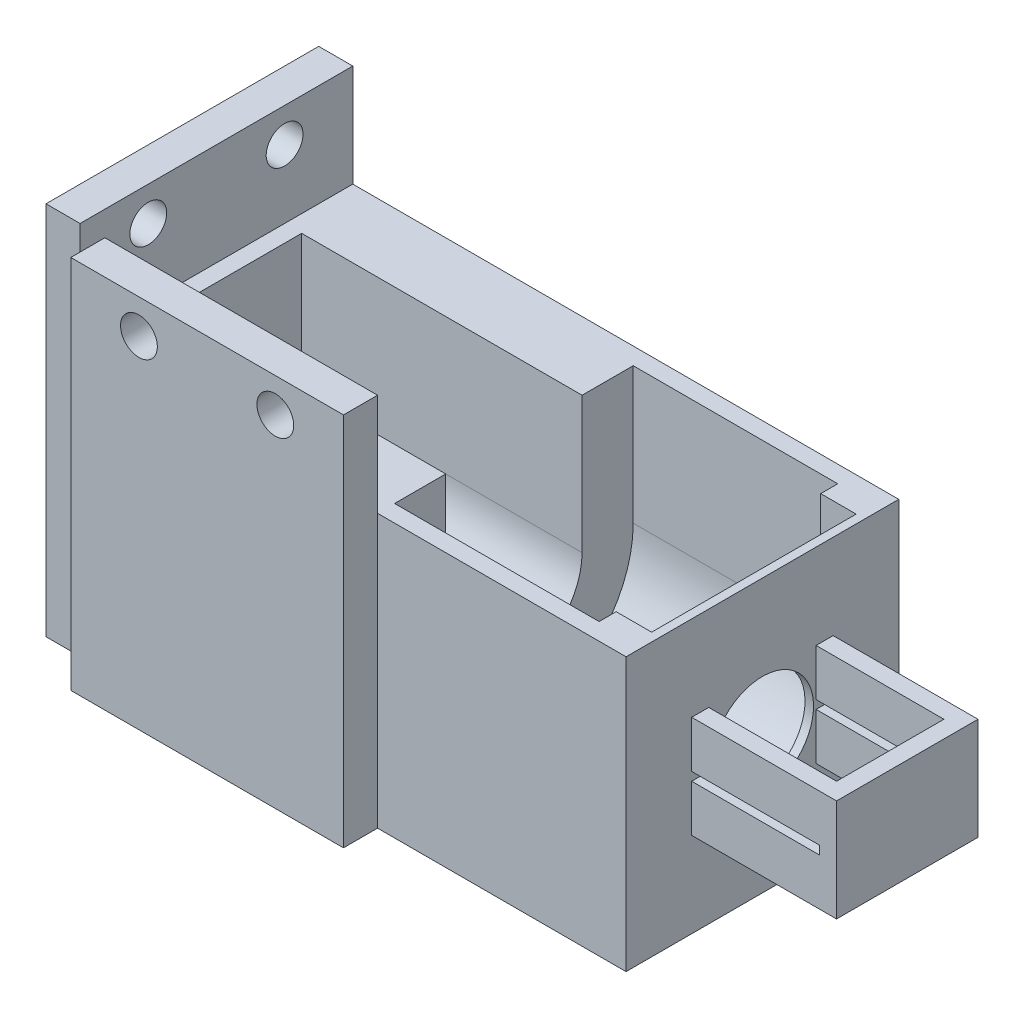
SolidWorks part; units mm, degrees
ref_plane "Front Plane" through (0, 0, 0) normal (0, 0, 1) x (1, 0, 0)
ref_plane "Top Plane" through (0, 0, 0) normal (0, 1, 0) x (1, 0, 0)
ref_plane "Right Plane" through (0, 0, 0) normal (1, 0, 0) x (0, 0, -1)
sketch "Sketch1" plane through (0, 0, 0) normal (0, 0, 1) x (1, 0, 0)
  line L1 (-76.2, -50.8) -> (40.64, -50.8)
  line L2 (-76.2, -50.8) -> (-76.2, 0)
  line L3 (-76.2, 0) -> (40.64, 0)
  line L4 (40.64, -50.8) -> (40.64, 0)
  line L5 (-76.2, -50.8) -> (40.64, 0) construction
  line L6 (-76.2, 0) -> (40.64, -50.8) construction
  point P0 (0, 0)
  dimension "D1" = 116.84
  dimension "D2" = 50.8
  dimension "D3" = 76.2
extrude "Boss-Extrude1" add sketch "Sketch1" along normal mid plane 50.8
sketch "Sketch2" plane through (0, 0, 0) normal (0, 0, 1) x (1, 0, 0)
  line L0 (-152.4829, -25.4) -> (19.6294, -25.4) construction
  line L1 (-49.3609, -3.175) -> (-49.3609, -12.7)
  line L2 (40.64, 0) -> (-76.2, 0) construction
  line L3 (40.64, 0) -> (-76.2, 0) construction
  line L4 (-11.2609, -3.175) -> (-11.2609, -6.35)
  line L5 (-11.2609, -25.4) -> (-11.2609, -3.175) construction
  line L6 (-128.4172, -25.4) -> (-157.8092, -25.4)
  line L7 (19.6294, -25.4) -> (20.7431, -25.4)
  line L8 (-607.3619, -25.4) -> (19.6294, -25.4) construction
  line L9 (-49.3609, -3.175) -> (-11.2609, -3.175)
  line L10 (19.6294, -25.4) -> (-128.4172, -25.4)
  line L11 (-11.2609, -6.35) -> (-4.6569, -6.35)
  line L12 (-4.6569, -6.35) -> (-4.6569, -15.494)
  line L13 (-4.6569, -15.494) -> (20.7431, -15.494)
  line L14 (-49.3609, -12.7) -> (-220.2024, -12.7)
  line L15 (-220.2024, -12.7) -> (-220.2024, -25.4)
  line L16 (-220.2024, -25.4) -> (-157.8092, -25.4)
  line L20 (20.7431, -15.494) -> (20.7431, -25.4)
  line L21 (-76.2, 0) -> (-76.2, -50.8) construction
  point P23 (-11.2609, -25.4)
  dimension "D1" = 22.225
  dimension "D2" = 38.1
  dimension "D3" = 25.4
  dimension "D4" = 32.004
  dimension "D5" = 9.906
  dimension "D6" = 3.175
  dimension "D7" = 26.8391
  dimension "D8" = 25.4
  dimension "D9" = 12.7
revolve "Cut-Revolve1" cut sketch "Sketch2" angle 360 about L0
sketch "Sketch38" plane through (20.7431, 0, 0) normal (1, 0, 0) x (0, 0, -1)
  line L1 (-10, -35.4) -> (10, -35.4)
  line L2 (-10, -35.4) -> (-10, -15.4)
  line L3 (-10, -15.4) -> (10, -15.4)
  line L4 (10, -35.4) -> (10, -15.4)
  line L5 (-10, -35.4) -> (10, -15.4) construction
  line L6 (-10, -15.4) -> (10, -35.4) construction
  circle A0 centre (0, -25.4) radius 9.906 construction
  point P1 (0, -25.4)
  dimension "D1" = 20
  dimension "D2" = 20
extrude "Cut-Extrude33" cut sketch "Sketch38" against normal offset from surface (23.8125 mm away) 1.5875 up to face at (-4.6569, -25.4, 19.05)
sketch "Sketch37" plane through (40.64, 0, 0) normal (1, 0, 0) x (0, 0, -1)
  line L0 (25.4, -50.8) -> (25.4, 0) construction
  line L1 (-25.4, 0) -> (25.4, 0)
  line L2 (-25.4, 0) -> (-25.4, -25.4)
  line L3 (-25.4, -25.4) -> (25.4, -25.4)
  line L4 (25.4, 0) -> (25.4, -25.4)
  line L5 (10, -35.4) -> (10, -15.4) construction
  point P7 (0, -25.4)
  point P11 (0, 0)
  point P14 (10, -25.4)
extrude "Cut-Extrude32" cut sketch "Sketch37" against normal through all
sketch "Sketch39" plane through (0, -25.4, 0) normal (0, 1, 0) x (1, 0, 0)
  line L24 (-49.3609, -12.7) -> (-76.2, -12.7)
  line L25 (-76.2, -12.7) -> (-76.2, -25.4)
  line L26 (-76.2, -25.4) -> (40.64, -25.4)
  line L27 (40.64, -25.4) -> (40.64, 25.4)
  line L28 (40.64, 25.4) -> (-76.2, 25.4)
  line L29 (-76.2, 25.4) -> (-76.2, 12.7)
  line L30 (-76.2, 12.7) -> (-49.3609, 12.7)
  line L31 (-49.3609, 12.7) -> (-49.3609, 22.225)
  line L32 (-49.3609, 22.225) -> (-11.2609, 22.225)
  line L33 (-11.2609, 22.225) -> (-11.2609, 19.05)
  line L34 (-11.2609, 19.05) -> (-4.6569, 19.05)
  line L35 (-4.6569, 19.05) -> (-4.6569, 9.906)
  line L36 (-4.6569, 9.906) -> (-3.0694, 9.906)
  line L37 (-3.0694, 9.906) -> (-3.0694, 10)
  line L38 (-3.0694, 9.906) -> (-3.0694, 10)
  line L39 (20.7431, 10) -> (20.7431, -10)
  line L40 (-3.0694, 10) -> (20.7431, 10)
  line L41 (-3.0694, 10) -> (20.7431, 10)
  line L42 (-3.0694, -9.906) -> (-4.6569, -9.906)
  line L43 (-4.6569, -9.906) -> (-4.6569, -19.05)
  line L44 (-4.6569, -19.05) -> (-11.2609, -19.05)
  line L45 (-11.2609, -19.05) -> (-11.2609, -22.225)
  line L46 (-11.2609, -22.225) -> (-49.3609, -22.225)
  line L47 (-49.3609, -22.225) -> (-49.3609, -12.7)
  line L48 (-49.3609, -12.7) -> (-76.2, -12.7)
  line L49 (-76.2, -12.7) -> (-76.2, -25.4)
  line L50 (-76.2, -25.4) -> (40.64, -25.4)
  line L51 (40.64, -25.4) -> (40.64, 25.4)
  line L52 (40.64, 25.4) -> (-76.2, 25.4)
  line L53 (-76.2, 25.4) -> (-76.2, 12.7)
  line L54 (-76.2, 12.7) -> (-49.3609, 12.7)
  line L55 (-49.3609, 12.7) -> (-49.3609, 22.225)
  line L56 (-49.3609, 22.225) -> (-11.2609, 22.225)
  line L57 (-11.2609, 22.225) -> (-11.2609, 19.05)
  line L58 (-11.2609, 19.05) -> (-4.6569, 19.05)
  line L59 (-4.6569, 19.05) -> (-4.6569, 9.906)
  line L60 (-4.6569, 9.906) -> (-3.0694, 9.906)
  line L61 (20.7431, -10) -> (-3.0694, -10)
  line L62 (20.7431, -10) -> (-3.0694, -10)
  line L63 (20.7431, 10) -> (20.7431, -10)
  line L64 (-3.0694, -10) -> (-3.0694, -9.906)
  line L65 (-3.0694, -10) -> (-3.0694, -9.906)
  line L66 (-3.0694, -9.906) -> (-4.6569, -9.906)
  line L67 (-4.6569, -9.906) -> (-4.6569, -19.05)
  line L68 (-4.6569, -19.05) -> (-11.2609, -19.05)
  line L69 (-11.2609, -19.05) -> (-11.2609, -22.225)
  line L70 (-11.2609, -22.225) -> (-49.3609, -22.225)
  line L71 (-49.3609, -22.225) -> (-49.3609, -12.7)
  dimension "D1" = 0
extrude "Boss-Extrude5" add sketch "Sketch39" along normal blind 25.4
ref_axis "Axis1" through (-3.0694, -25.4, 0) along (-1, 0, 0)
ref_plane "Plane_Mid" through (0, -25.4, 0) normal (0, 1, 0) x (1, 0, 0)
sketch "Sketch45" plane through (0, 0, 0) normal (0, 0, 1) x (1, 0, 0)
  line L2 (40.64, 0) -> (-3.0694, 0)
  line L4 (40.64, 0) -> (40.64, -19.05)
  line L5 (40.64, -19.05) -> (-3.0694, -19.05)
  line L6 (-3.0694, -25.4) -> (-4.6569, -25.4) construction
  line L8 (-3.0694, 0) -> (-3.0694, -19.05)
  dimension "D2" = 6.35
extrude "Cut-Extrude54" cut sketch "Sketch45" against normal through all both and the other way through all
sketch "Sketch53" plane through (20.7431, 0, 0) normal (-1, 0, 0) x (0, 0, 1)
  circle A0 centre (0, -25.4) radius 2
  dimension "D1" = 4
extrude "Cut-Extrude46" cut sketch "Sketch53" against normal blind 0.0254
sketch "Sketch72" plane through (0, -19.05, 0) normal (0, 1, 0) x (1, 0, 0)
  line L0 (-3.0694, -25.4) -> (-3.0694, -13.175)
  line L1 (-3.0694, -10) -> (-3.0694, -25.4) construction
  line L2 (-3.0694, -13.175) -> (23.9181, -13.175)
  line L3 (23.9181, -13.175) -> (23.9181, 13.175)
  line L4 (23.9181, 13.175) -> (-3.0694, 13.175)
  line L5 (-3.0694, 25.4) -> (-3.0694, 10) construction
  line L6 (-3.0694, 13.175) -> (-3.0694, 25.4)
  line L7 (-3.0694, 25.4) -> (40.64, 25.4)
  line L8 (40.64, 25.4) -> (40.64, -25.4)
  line L9 (40.64, -25.4) -> (-3.0694, -25.4)
  line L10 (-3.0694, -10) -> (20.7431, -10) construction
  line L11 (-3.0694, -10) -> (-3.0694, -13.175) construction
  line L12 (20.7431, -10) -> (23.9181, -10) construction
  line L13 (20.7431, 10) -> (20.7431, 13.175) construction
  dimension "D1" = 3.175
extrude "Cut-Extrude55" cut sketch "Sketch72" against normal through all
sketch "Sketch61" plane through (-4.6569, 0, 0) normal (-1, 0, 0) x (0, 0, 1)
  circle A0 centre (0, -25.4) radius 9.525
  circle A1 centre (0, -25.4) radius 9.906
  arc A2 (-9.906, -25.4) -> (9.906, -25.4) centre (0, -25.4) ccw construction
  dimension "D1" = 19.05
extrude "Boss-Extrude11" add sketch "Sketch61" against normal up to surface (1.5875 mm away) up to face at (-3.0694, -25.6816, 0)
sketch "Sketch70" plane through (0, 0, 0) normal (0, 1, 0) x (1, 0, 0)
  line L1 (-4.6569, 9.906) -> (-3.0694, 9.906)
  line L2 (-4.6569, 9.906) -> (-4.6569, -9.906)
  line L3 (-4.6569, -9.906) -> (-3.0694, -9.906)
  line L4 (-3.0694, 9.906) -> (-3.0694, -9.906)
extrude "Boss-Extrude17" add sketch "Sketch70" against normal up to next
sketch "Sketch76" plane through (0, -35.4, 0) normal (0, 1, 0) x (1, 0, 0)
  line L5 (-3.0694, -10) -> (20.7431, -10)
  line L6 (20.7431, -10) -> (20.7431, 10)
  line L9 (20.7431, 10) -> (-3.0694, 10)
  line L10 (-3.0694, 10) -> (-3.0694, -10)
  line L11 (-3.0694, -10) -> (20.7431, -10)
  line L12 (20.7431, -10) -> (20.7431, 10)
  line L13 (20.7431, 10) -> (-3.0694, 10)
  line L14 (-3.0694, 10) -> (-3.0694, -10)
  dimension "D1" = 0
extrude "Cut-Extrude58" cut sketch "Sketch76" against normal through all
sketch "Sketch77" plane through (0, 0, 0) normal (0, 0, 1) x (1, 0, 0)
  line L1 (-3.0694, -26.1938) -> (20.7431, -26.1938)
  line L2 (-3.0694, -26.1938) -> (-3.0694, -24.6063)
  line L3 (-3.0694, -24.6063) -> (20.7431, -24.6063)
  line L4 (20.7431, -26.1938) -> (20.7431, -24.6063)
  line L5 (-3.0694, -26.1938) -> (20.7431, -24.6063) construction
  line L6 (-3.0694, -24.6063) -> (20.7431, -26.1938) construction
  line L9 (-3.0694, -25.4) -> (-4.6569, -25.4) construction
  line L10 (-3.0694, -19.05) -> (-3.0694, -50.8) construction
  line L11 (20.7431, -19.05) -> (20.7431, -50.8) construction
  point P0 (8.8368, -25.4)
  point P7 (0, 0)
  dimension "D2" = 1.5875
extrude "Cut-Extrude59" cut sketch "Sketch77" against normal through all both and the other way through all
sketch "Sketch78" plane through (-76.2, 0, 0) normal (-1, 0, 0) x (0, 0, 1)
  line L7 (25.4, -50.8) -> (25.4, 0)
  line L8 (25.4, 0) -> (12.7, 0)
  line L9 (12.7, 0) -> (12.7, -25.4)
  line L10 (-12.7, -25.4) -> (-12.7, 0)
  line L11 (-12.7, 0) -> (-25.4, 0)
  line L12 (-25.4, 0) -> (-25.4, -50.8)
  line L13 (-25.4, -50.8) -> (25.4, -50.8)
  line L14 (25.4, -50.8) -> (25.4, 0)
  line L15 (25.4, 0) -> (12.7, 0)
  line L16 (12.7, 0) -> (12.7, -25.4)
  line L17 (-12.7, -25.4) -> (-12.7, 0)
  line L18 (-12.7, 0) -> (-25.4, 0)
  line L19 (-25.4, 0) -> (-25.4, -50.8)
  line L20 (-25.4, -50.8) -> (25.4, -50.8)
  arc A1 (-12.7, -25.4) -> (12.7, -25.4) centre (0, -25.4) ccw
  arc A2 (-12.7, -25.4) -> (12.7, -25.4) centre (0, -25.4) ccw
  dimension "D1" = 0
sketch "Sketch86" plane through (0, -19.05, 0) normal (0, 1, 0) x (1, 0, 0)
  line L16 (20.7431, 10) -> (20.7431, -10)
  line L25 (20.7431, -10) -> (-3.0694, -10)
  line L26 (-3.0694, -10) -> (-3.0694, -13.175)
  line L27 (-3.0694, -13.175) -> (23.9181, -13.175)
  line L28 (23.9181, -13.175) -> (23.9181, 13.175)
  line L29 (23.9181, 13.175) -> (-3.0694, 13.175)
  line L30 (-3.0694, 13.175) -> (-3.0694, 10)
  line L31 (-3.0694, 10) -> (20.7431, 10)
  line L32 (20.7431, 10) -> (20.7431, -10)
  line L41 (20.7431, -10) -> (-3.0694, -10)
  line L42 (-3.0694, -10) -> (-3.0694, -13.175)
  line L43 (-3.0694, -13.175) -> (23.9181, -13.175)
  line L44 (23.9181, -13.175) -> (23.9181, 13.175)
  line L45 (23.9181, 13.175) -> (-3.0694, 13.175)
  line L46 (-3.0694, 13.175) -> (-3.0694, 10)
  line L47 (-3.0694, 10) -> (20.7431, 10)
  dimension "D1" = 0
extrude "Boss-Extrude24" add sketch "Sketch86" along normal blind 3.175
extrude "Boss-Extrude18" add sketch "Sketch78" along normal blind 25.4
sketch "Sketch79" plane through (-101.6, 0, 0) normal (-1, 0, 0) x (0, 0, 1)
  line L1 (-25.4, -50.8) -> (25.4, -50.8)
  line L2 (-25.4, -50.8) -> (-25.4, 0)
  line L3 (-25.4, 0) -> (25.4, 0)
  line L4 (25.4, -50.8) -> (25.4, 0)
extrude "Boss-Extrude19" add sketch "Sketch79" along normal blind 3.175
sketch "Sketch80" plane through (-104.775, 0, 0) normal (-1, 0, 0) x (0, 0, 1)
  line L0 (-25.4, 0) -> (-25.4, -50.8) construction
  line L1 (25.4, -50.8) -> (-25.4, -50.8)
  line L2 (25.4, -50.8) -> (25.4, 50.8)
  line L3 (25.4, 50.8) -> (-25.4, 50.8)
  line L4 (-25.4, -50.8) -> (-25.4, 50.8)
  line L5 (25.4, 0) -> (-25.4, 0) construction
  dimension "D1" = 50.8
extrude "Boss-Extrude20" add sketch "Sketch80" along normal blind 6.35
sketch "Sketch81" plane through (-104.775, 0, 0) normal (1, 0, 0) x (0, 0, -1)
  line L0 (-25.4, 50.8) -> (25.4, 50.8) construction
  line L1 (-25.4, 0) -> (-25.4, 50.8) construction
  circle A0 centre (-12.7, 38.1) radius 3.429
  circle A1 centre (12.7, 38.1) radius 3.429
  circle A2 centre (12.7, 12.7) radius 3.429
  circle A3 centre (-12.7, 12.7) radius 3.429
  dimension "D1" = 6.858
  dimension "D2" = 12.7
  dimension "D3" = 12.7
  dimension "D4" = 2
  dimension "D5" = 2
extrude "Cut-Extrude60" cut sketch "Sketch81" against normal through all
sketch "Sketch82" plane through (0, 0, 25.4) normal (0, 0, 1) x (1, 0, 0)
  line L0 (-111.125, -50.8) -> (-3.0694, -50.8) construction
  line L1 (-100.1609, -50.8) -> (-49.3609, -50.8)
  line L2 (-100.1609, -50.8) -> (-100.1609, 50.8)
  line L3 (-100.1609, 50.8) -> (-49.3609, 50.8)
  line L4 (-49.3609, -50.8) -> (-49.3609, 50.8)
  line L5 (-111.125, 50.8) -> (-104.775, 50.8) construction
  dimension "D1" = 50.8
extrude "Boss-Extrude21" add sketch "Sketch82" along normal blind 6.35
sketch "Sketch83" plane through (0, 0, 25.4) normal (0, 0, -1) x (-1, 0, 0)
  line L0 (49.3609, 50.8) -> (100.1609, 50.8) construction
  line L1 (49.3609, 0) -> (49.3609, 50.8) construction
  circle A0 centre (62.0609, 38.1) radius 3.429
  circle A1 centre (87.4609, 38.1) radius 3.429
  circle A2 centre (87.4609, 12.7) radius 3.429
  circle A3 centre (62.0609, 12.7) radius 3.429
  dimension "D1" = 6.858
  dimension "D2" = 12.7
  dimension "D3" = 12.7
  dimension "D4" = 2
  dimension "D5" = 2
extrude "Cut-Extrude61" cut sketch "Sketch83" against normal through all
sketch "Sketch84" plane through (0, 50.8, 0) normal (0, 1, 0) x (1, 0, 0)
  line L1 (-129.7202, -53.2466) -> (-19.4704, -53.2466)
  line L2 (-129.7202, -53.2466) -> (-129.7202, 56.3815)
  line L3 (-129.7202, 56.3815) -> (-19.4704, 56.3815)
  line L4 (-19.4704, -53.2466) -> (-19.4704, 56.3815)
extrude "Cut-Extrude62" cut sketch "Sketch84" against normal blind 31.75
sketch "Sketch87" plane through (0, -50.8, 0) normal (0, -1, 0) x (1, 0, 0)
  line L1 (23.9181, 13.175) -> (-3.0694, 13.175)
  line L2 (23.9181, 13.175) -> (23.9181, -25.4)
  line L3 (23.9181, -25.4) -> (-3.0694, -25.4)
  line L4 (-3.0694, 13.175) -> (-3.0694, -25.4)
  line L5 (23.9181, 13.175) -> (-3.0694, -25.4) construction
  line L6 (23.9181, -25.4) -> (-3.0694, 13.175) construction
  point P4 (10.4243, -6.1125)
extrude "Cut-Extrude63" cut sketch "Sketch87" against normal blind 15.875
sketch "Sketch89" plane through (0, 0, 0) normal (0, 1, 0) x (1, 0, 0)
  line L0 (-3.0694, 0) -> (-4.6569, 0) construction
  line L1 (-38.3605, -2.5981) -> (-18.7213, -2.5981)
  line L2 (-38.3605, -2.5981) -> (-38.3605, 2.5981)
  line L3 (-38.3605, 2.5981) -> (-18.7213, 2.5981)
  line L4 (-18.7213, -2.5981) -> (-18.7213, 2.5981)
  line L5 (-38.3605, -2.5981) -> (-18.7213, 2.5981) construction
  line L6 (-38.3605, 2.5981) -> (-18.7213, -2.5981) construction
  line L8 (-84.575, -2.5981) -> (-64.9357, -2.5981)
  line L9 (-84.575, -2.5981) -> (-84.575, 2.5981)
  line L10 (-84.575, 2.5981) -> (-64.9357, 2.5981)
  line L11 (-64.9357, -2.5981) -> (-64.9357, 2.5981)
  line L12 (-84.575, -2.5981) -> (-64.9357, 2.5981) construction
  line L13 (-84.575, 2.5981) -> (-64.9357, -2.5981) construction
  point P4 (-28.5409, 0)
  point P5 (0, 0)
  point P8 (-74.7553, 0)
  point P13 (-74.7553, 0)
  point P14 (0, 0)
extrude "Cut-Extrude64" cut sketch "Sketch89" against normal through all
